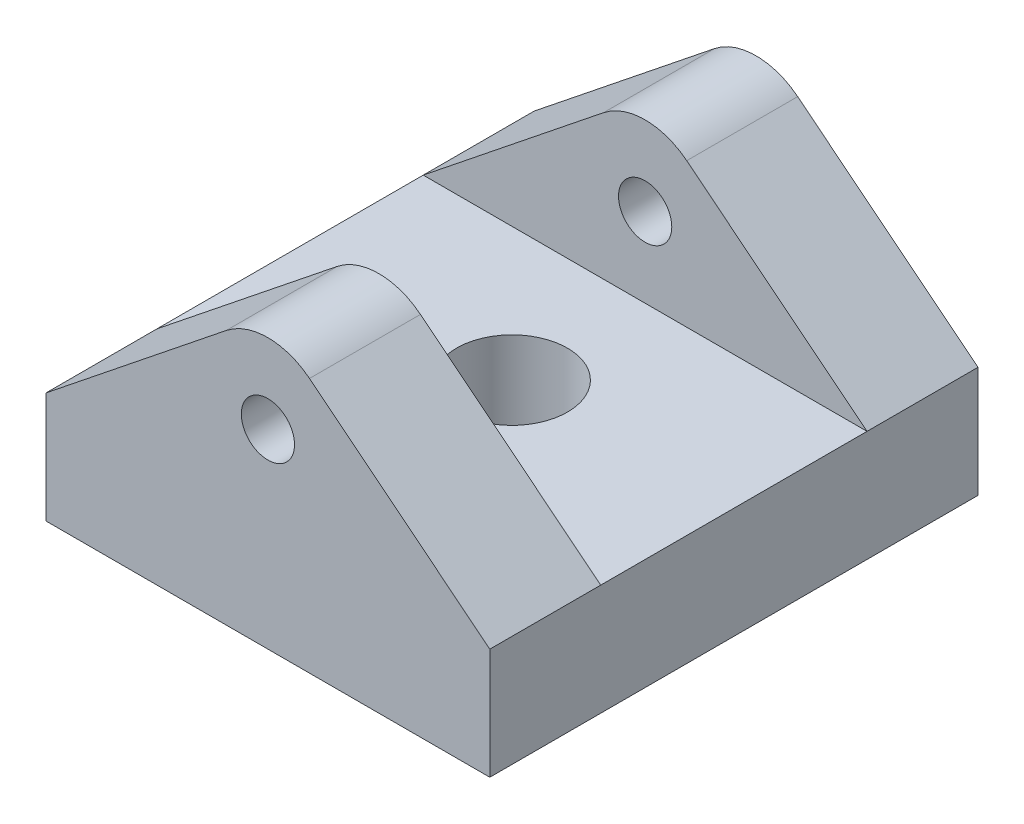
SolidWorks part; units mm, degrees
ref_plane "Front Plane" through (0, 0, 0) normal (0, 0, 1) x (1, 0, 0)
ref_plane "Top Plane" through (0, 0, 0) normal (0, 1, 0) x (1, 0, 0)
ref_plane "Right Plane" through (0, 0, 0) normal (1, 0, 0) x (0, 0, -1)
sketch "Sketch1" plane through (0, 0, 0) normal (0, 1, 0) x (1, 0, 0)
  line L0 (-10, 6) -> (10, 6)
  line L1 (-10, 11) -> (10, 11)
  line L2 (-10, 11) -> (-10, -11)
  line L3 (-10, -11) -> (10, -11)
  line L4 (10, 11) -> (10, -11)
  line L5 (-10, 11) -> (10, -11) construction
  line L6 (-10, -11) -> (10, 11) construction
  line L7 (-10, -6) -> (10, -6)
  point P0 (0, 0)
  dimension "D1" = 20
  dimension "D2" = 22
  dimension "D3" = 5
  dimension "D4" = 5
extrude "Boss-Extrude1" add sketch "Sketch1" along normal blind 5 contours L4 L1 L2 L0 | L2 L7 L4 L0 | L7 L2 L3 L4 region at (0, 0, -8.5) region at (0, 0, 0) region at (0, 0, 8.5)
sketch "Sketch2" plane through (0, 0, 11) normal (0, 0, 1) x (1, 0, 0)
  line L0 (-10, 5) -> (0, 13)
  line L1 (0, 13) -> (10, 5)
  line L2 (10, 5) -> (-10, 5)
  point P5 (0, 0)
  point P6 (0, 5)
  dimension "D1" = 8
extrude "Boss-Extrude2" add sketch "Sketch2" along direction (0, 0, 1) on the side against the normal blind 5
extrude "Boss-Extrude3" add sketch "Sketch2<2>" along normal blind 5 from surface starting at face at (0, 2.5, -11)
sketch "Sketch2<2>" plane through (0, 0, 11) normal (0, 0, 1) x (1, 0, 0) same geometry as "Sketch2"
fillet "Fillet1" radius 3 2 edges at (0, 13, -8.5) (0, 13, 8.5)
hole_wizard "Ø5.0 (5) Diameter Hole1" positions "Sketch3" profile "Sketch4" hole size "Ø5.0" standard "ANSI Metric" end condition up to next
sketch "Sketch3" plane through (0, 5, 0) normal (0, 1, 0) x (1, 0, 0)
  point P0 (0, 0)
sketch "Sketch4" plane through (0, 5, 0) normal (1, 0, 0) x (0, 0, 1)
  line L0 (0, 0) -> (0, 5)
  line L1 (0, 5) -> (2.5, 5)
  line L2 (2.5, 5) -> (2.5, 0)
  line L5 (2.5, 0) -> (0, 0)
  line L11 (0, -6.35) -> (0, 107.95) construction
  dimension "Thru Hole Dia." = 5
  dimension "Thru Hole Depth" = 5
hole_wizard "Ø3.2 (3.2) for M2 heat set" positions "Sketch5" profile "Sketch6" hole size "M2" standard "ANSI Metric" end condition up to next
sketch "Sketch5" plane through (0, 0, -6) normal (0, 0, 1) x (1, 0, 0)
  line L0 (0, 12.1581) -> (0, 5) construction
  line L1 (10, 5) -> (-10, 5) construction
  arc A0 (1.8741, 11.5007) -> (-1.8741, 11.5007) centre (0, 9.1581) ccw construction
  point P0 (0, 8.5791)
  point P11 (0, 0)
sketch "Sketch6" plane through (0, 8.5791, -6) normal (1, 0, 0) x (0, -1, 0)
  line L0 (0, 0) -> (0, 5)
  line L1 (0, 5) -> (1.2, 5)
  line L2 (1.2, 5) -> (1.2, 0)
  line L5 (1.2, 0) -> (0, 0)
  line L11 (0, -6.35) -> (0, 107.95) construction
  dimension "Thru Hole Dia." = 2.4
  dimension "Thru Hole Depth" = 5
mirror "Mirror1" about plane through (0, 0, 0) normal (0, 0, 1) of "Ø3.2 (3.2) for M2 heat set"
